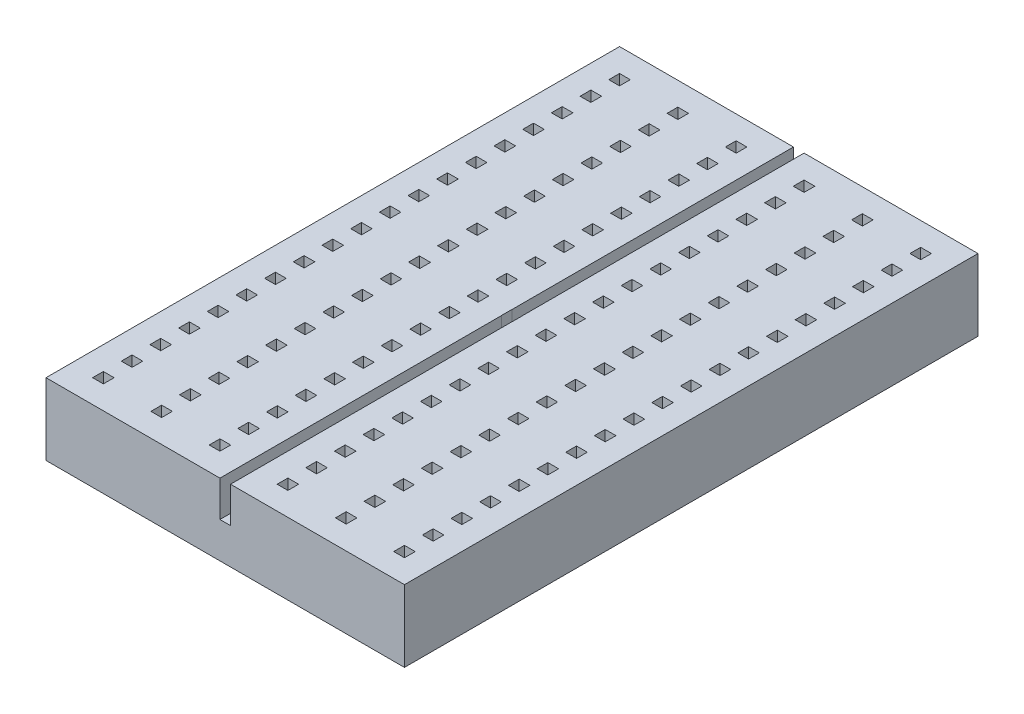
SolidWorks part; units mm, degrees
ref_plane "Front" through (0, 0, 0) normal (0, 0, 1) x (1, 0, 0)
ref_plane "Top" through (0, 0, 0) normal (0, 1, 0) x (1, 0, 0)
ref_plane "Right" through (0, 0, 0) normal (1, 0, 0) x (0, 0, -1)
sketch "Sketch1" plane through (0, 0, 0) normal (0, 1, 0) x (1, 0, 0)
  line L1 (-25, 40) -> (25, 40)
  line L2 (-25, 40) -> (-25, -40)
  line L3 (-25, -40) -> (25, -40)
  line L4 (25, 40) -> (25, -40)
  line L5 (-25, 40) -> (25, -40) construction
  line L6 (-25, -40) -> (25, 40) construction
  point P0 (0, 0)
  dimension "D1" = 80
  dimension "D2" = 50
extrude "Boss-Extrude1" add sketch "Sketch1" along normal blind 10
sketch "Sketch2" plane through (0, 10, 0) normal (0, 1, 0) x (1, 0, 0)
  line L0 (-25, -40) -> (25, -40) construction
  line L1 (-0.7388, 40) -> (0.7388, 40)
  line L2 (-0.7388, 40) -> (-0.7388, -40)
  line L3 (-0.7388, -40) -> (0.7388, -40)
  line L4 (0.7388, 40) -> (0.7388, -40)
  line L5 (-0.7388, 40) -> (0.7388, -40) construction
  line L6 (-0.7388, -40) -> (0.7388, 40) construction
  point P1 (0, 0)
extrude "Cut-Extrude1" cut sketch "Sketch2" against normal blind 5
sketch "Sketch3" plane through (0, 10, 0) normal (0, 1, 0) x (1, 0, 0)
  line L0 (-25, 0) -> (25, 0) construction
  line L1 (-25, 40) -> (-25, -40) construction
  line L2 (25, -40) -> (25, 40) construction
  line L3 (-21, 36) -> (-4.7388, 36) construction
  line L4 (0, 40) -> (0, -40) construction
  line L5 (-21, 32) -> (-4.7388, 32) construction
  line L6 (-21, 32) -> (-21, 36) construction
  line L7 (-0.7388, 40) -> (-0.7388, -40) construction
  line L8 (-0.7388, -40) -> (0.7388, -40) construction
  line L9 (-12.8694, 36) -> (-12.8694, 32) construction
  line L10 (-4.7388, 36) -> (-4.7388, 32) construction
  line L11 (-21, 28) -> (-4.7388, 28) construction
  line L12 (-21, 24) -> (-4.7388, 24) construction
  line L13 (-21, 24) -> (-21, 28) construction
  line L14 (-12.8694, 28) -> (-12.8694, 24) construction
  line L15 (-4.7388, 28) -> (-4.7388, 24) construction
  line L16 (-21, 20) -> (-4.7388, 20) construction
  line L17 (-21, 16) -> (-4.7388, 16) construction
  line L18 (-21, 16) -> (-21, 20) construction
  line L19 (-12.8694, 20) -> (-12.8694, 16) construction
  line L20 (-4.7388, 20) -> (-4.7388, 16) construction
  line L21 (-0.7388, 40) -> (-25, 40) construction
  line L22 (-21, 12) -> (-4.7388, 12) construction
  line L23 (-21, 8) -> (-4.7388, 8) construction
  line L24 (-21, 8) -> (-21, 12) construction
  line L25 (-12.8694, 12) -> (-12.8694, 8) construction
  line L26 (-4.7388, 12) -> (-4.7388, 8) construction
  line L27 (-21, 4) -> (-4.7388, 4) construction
  line L28 (-21, 0) -> (-4.7388, 0) construction
  line L29 (-21, -4) -> (-21, 4) construction
  line L30 (-12.8694, 4) -> (-12.8694, -4) construction
  line L31 (-4.7388, 4) -> (-4.7388, -4) construction
  line L32 (-21, -4) -> (-4.7388, -4) construction
  line L33 (-4.7388, -12) -> (-4.7388, -8) construction
  line L34 (-12.8694, -12) -> (-12.8694, -8) construction
  line L35 (-21, -8) -> (-21, -12) construction
  line L36 (-21, -8) -> (-4.7388, -8) construction
  line L37 (-21, -12) -> (-4.7388, -12) construction
  line L38 (-4.7388, -20) -> (-4.7388, -16) construction
  line L39 (-12.8694, -20) -> (-12.8694, -16) construction
  line L40 (-21, -16) -> (-21, -20) construction
  line L41 (-21, -16) -> (-4.7388, -16) construction
  line L42 (-21, -20) -> (-4.7388, -20) construction
  line L43 (-4.7388, -28) -> (-4.7388, -24) construction
  line L44 (-12.8694, -28) -> (-12.8694, -24) construction
  line L45 (-21, -24) -> (-21, -28) construction
  line L46 (-21, -24) -> (-4.7388, -24) construction
  line L47 (-21, -28) -> (-4.7388, -28) construction
  line L48 (-4.7388, -36) -> (-4.7388, -32) construction
  line L49 (-12.8694, -36) -> (-12.8694, -32) construction
  line L50 (-21, -32) -> (-21, -36) construction
  line L51 (-21, -32) -> (-4.7388, -32) construction
  line L52 (-21, -36) -> (-4.7388, -36) construction
  line L53 (21, -36) -> (4.7388, -36) construction
  line L54 (21, -32) -> (4.7388, -32) construction
  line L55 (21, -32) -> (21, -36) construction
  line L56 (12.8694, -36) -> (12.8694, -32) construction
  line L57 (4.7388, -36) -> (4.7388, -32) construction
  line L58 (21, -28) -> (4.7388, -28) construction
  line L59 (21, -24) -> (4.7388, -24) construction
  line L60 (21, -24) -> (21, -28) construction
  line L61 (12.8694, -28) -> (12.8694, -24) construction
  line L62 (4.7388, -28) -> (4.7388, -24) construction
  line L63 (21, -20) -> (4.7388, -20) construction
  line L64 (21, -16) -> (4.7388, -16) construction
  line L65 (4.7388, -20) -> (4.7388, -16) construction
  line L66 (21, -12) -> (4.7388, -12) construction
  line L67 (21, -8) -> (4.7388, -8) construction
  line L68 (4.7388, -12) -> (4.7388, -8) construction
  line L69 (21, -4) -> (4.7388, -4) construction
  line L70 (4.7388, 4) -> (4.7388, -4) construction
  line L71 (21, 0) -> (4.7388, 0) construction
  line L72 (21, 4) -> (4.7388, 4) construction
  line L73 (4.7388, 12) -> (4.7388, 8) construction
  line L74 (21, 8) -> (4.7388, 8) construction
  line L75 (21, 12) -> (4.7388, 12) construction
  line L76 (4.7388, 20) -> (4.7388, 16) construction
  line L77 (21, 16) -> (4.7388, 16) construction
  line L78 (21, 20) -> (4.7388, 20) construction
  line L79 (4.7388, 28) -> (4.7388, 24) construction
  line L80 (21, 24) -> (4.7388, 24) construction
  line L81 (21, 28) -> (4.7388, 28) construction
  line L82 (4.7388, 36) -> (4.7388, 32) construction
  line L83 (21, 32) -> (4.7388, 32) construction
  line L84 (21, 36) -> (4.7388, 36) construction
  line L85 (21, -16) -> (21, -20) construction
  line L86 (12.8694, -20) -> (12.8694, -16) construction
  line L87 (21, -8) -> (21, -12) construction
  line L88 (12.8694, -12) -> (12.8694, -8) construction
  line L89 (12.8694, 4) -> (12.8694, -4) construction
  line L90 (21, -4) -> (21, 4) construction
  line L91 (12.8694, 12) -> (12.8694, 8) construction
  line L92 (21, 8) -> (21, 12) construction
  line L93 (12.8694, 20) -> (12.8694, 16) construction
  line L94 (21, 16) -> (21, 20) construction
  line L95 (12.8694, 28) -> (12.8694, 24) construction
  line L96 (21, 24) -> (21, 28) construction
  line L97 (12.8694, 36) -> (12.8694, 32) construction
  line L98 (21, 32) -> (21, 36) construction
  point P6 (-21, 36)
  point P7 (-12.87, 36)
  point P8 (-4.7388, 36)
  point P9 (-21, 32)
  point P10 (-12.8694, 32)
  point P11 (-12.9283, 0)
  point P12 (-4.7388, 32)
  point P21 (-21, 28)
  point P22 (-12.87, 28)
  point P23 (-4.7388, 28)
  point P24 (-21, 24)
  point P25 (-12.8694, 24)
  point P26 (-4.7388, 24)
  point P33 (-21, 20)
  point P34 (-12.87, 20)
  point P35 (-4.7388, 20)
  point P36 (-21, 16)
  point P37 (-12.8694, 16)
  point P38 (-4.7388, 16)
  point P47 (-21, 12)
  point P48 (-12.87, 12)
  point P49 (-4.7388, 12)
  point P50 (-21, 8)
  point P51 (-12.8694, 8)
  point P52 (-4.7388, 8)
  point P59 (-21, 4)
  point P60 (-12.87, 4)
  point P61 (-4.7388, 4)
  point P62 (-21, 0)
  point P63 (-12.8694, 0)
  point P64 (-4.7388, 0)
  point P74 (-12.8694, 0)
  point P75 (-4.7388, -4)
  point P76 (-12.87, -4)
  point P77 (-21, -4)
  point P102 (-4.7388, -8)
  point P103 (-12.8694, -8)
  point P104 (-21, -8)
  point P105 (-4.7388, -12)
  point P106 (-12.87, -12)
  point P107 (-21, -12)
  point P108 (-4.7388, -16)
  point P109 (-12.8694, -16)
  point P110 (-21, -16)
  point P111 (-4.7388, -20)
  point P112 (-12.87, -20)
  point P113 (-21, -20)
  point P114 (-4.7388, -24)
  point P115 (-12.8694, -24)
  point P116 (-21, -24)
  point P117 (-4.7388, -28)
  point P118 (-12.87, -28)
  point P119 (-21, -28)
  point P120 (-4.7388, -32)
  point P121 (-12.8694, -32)
  point P122 (-21, -32)
  point P123 (-4.7388, -36)
  point P124 (-12.87, -36)
  point P125 (-21, -36)
  point P132 (0, 0)
  point P172 (21, -36)
  point P173 (12.87, -36)
  point P174 (4.7388, -36)
  point P175 (21, -32)
  point P176 (12.8694, -32)
  point P177 (4.7388, -32)
  point P178 (21, -28)
  point P179 (12.87, -28)
  point P180 (4.7388, -28)
  point P181 (21, -24)
  point P182 (12.8694, -24)
  point P183 (4.7388, -24)
  point P184 (4.7388, -20)
  point P185 (4.7388, -16)
  point P186 (4.7388, -12)
  point P187 (4.7388, -8)
  point P188 (4.7388, -4)
  point P189 (4.7388, 0)
  point P190 (4.7388, 4)
  point P191 (4.7388, 8)
  point P192 (4.7388, 12)
  point P193 (4.7388, 16)
  point P194 (4.7388, 20)
  point P195 (4.7388, 24)
  point P196 (4.7388, 28)
  point P197 (4.7388, 32)
  point P198 (4.7388, 36)
  point P213 (21, -20)
  point P214 (12.87, -20)
  point P215 (21, -16)
  point P216 (12.8694, -16)
  point P217 (21, -12)
  point P218 (12.87, -12)
  point P219 (21, -8)
  point P220 (12.8694, -8)
  point P221 (21, -4)
  point P222 (12.87, -4)
  point P223 (12.8694, 0)
  point P224 (21, 0)
  point P225 (12.87, 4)
  point P226 (21, 4)
  point P227 (12.8694, 8)
  point P228 (21, 8)
  point P229 (12.87, 12)
  point P230 (21, 12)
  point P231 (12.8694, 16)
  point P232 (21, 16)
  point P233 (12.87, 20)
  point P234 (21, 20)
  point P235 (12.8694, 24)
  point P236 (21, 24)
  point P237 (12.87, 28)
  point P238 (21, 28)
  point P239 (12.9283, 0)
  point P240 (12.8694, 32)
  point P241 (21, 32)
  point P242 (12.87, 36)
  point P243 (21, 36)
  dimension "D1" = 8.13
  dimension "D2" = 4
  dimension "D3" = 4
  dimension "D4" = 8.1312
  dimension "D6" = 4
  dimension "D7" = 4
  dimension "D8" = 4
  dimension "D9" = 4
  dimension "D10" = 4
  dimension "D11" = 4
  dimension "D12" = 4
  dimension "D13" = 4
  dimension "D14" = 4
sketch "Sketch4" plane through (0, 10, 0) normal (0, 1, 0) x (1, 0, 0)
  line L1 (-21.75, 35.25) -> (-20.25, 35.25)
  line L2 (-21.75, 35.25) -> (-21.75, 36.75)
  line L3 (-21.75, 36.75) -> (-20.25, 36.75)
  line L4 (-20.25, 35.25) -> (-20.25, 36.75)
  line L5 (-21.75, 35.25) -> (-20.25, 36.75) construction
  line L6 (-21.75, 36.75) -> (-20.25, 35.25) construction
  point P0 (-21, 36)
  dimension "D1" = 1.5
  dimension "D2" = 1.5
extrude "Cut-Extrude2" cut sketch "Sketch4" against normal blind 2
pattern_sketch "Sketch-Pattern1" of "Cut-Extrude2" driven by "Sketch3"
